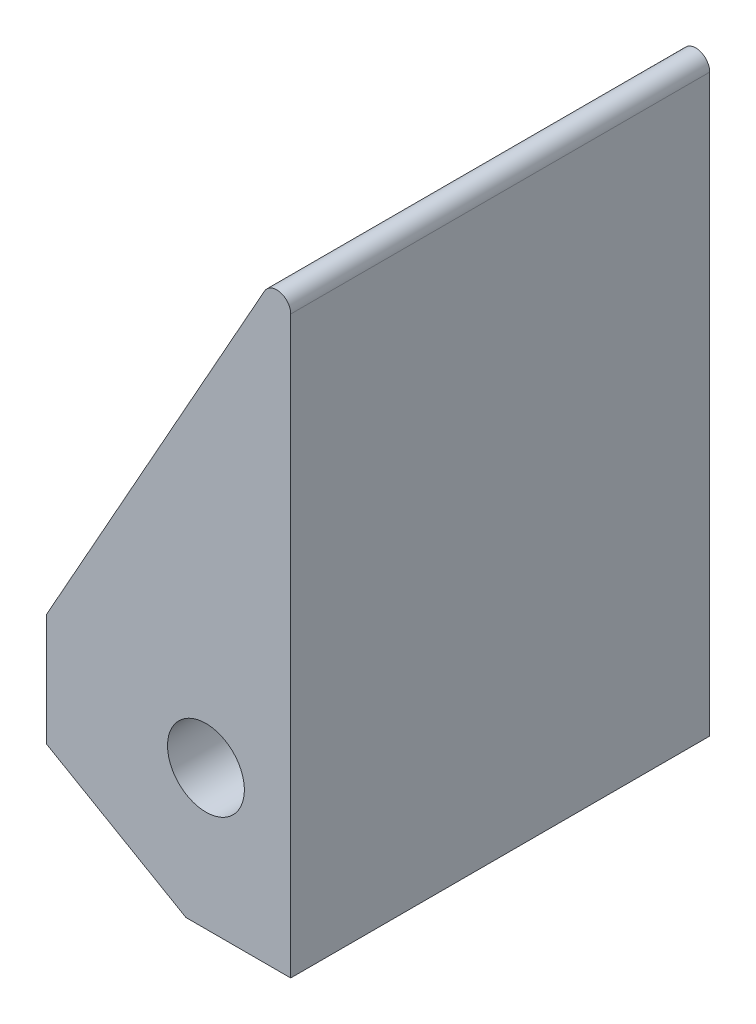
SolidWorks part; units mm, degrees
ref_plane "Front Plane" through (0, 0, 0) normal (0, 0, 1) x (1, 0, 0)
ref_plane "Top Plane" through (0, 0, 0) normal (0, 1, 0) x (1, 0, 0)
ref_plane "Right Plane" through (0, 0, 0) normal (1, 0, 0) x (0, 0, -1)
sketch "Sketch1" plane through (0, 0, 0) normal (0, 0, 1) x (1, 0, 0)
  line L0 (-8.1502, -18.2688) -> (1.8498, -24.0423)
  line L1 (1.8498, -24.0423) -> (9.3498, -24.0423)
  line L2 (-8.1502, -18.2688) -> (-8.1502, -10.2688)
  line L4 (9.3498, -24.0423) -> (9.3498, 20.9577)
  line L5 (-8.1502, -18.2688) -> (9.3498, 20.9577) construction
  line L6 (-0.9813, 2.5233) -> (9.3498, -24.0423) construction
  line L7 (-8.1502, -10.2688) -> (9.3498, 20.9577)
  point P0 (0, 0)
  dimension "D1" = 17.5
  dimension "D2" = 45
  dimension "D3" = 30
  dimension "D4" = 7.5
  dimension "D5" = 8
extrude "Boss-Extrude1" add sketch "Sketch1" along normal blind 30
sketch "Sketch2" plane through (0, 0, 0) normal (0, 0, -1) x (-1, 0, 0)
  line L0 (-1.8498, -24.0423) -> (-9.3498, -24.0423) construction
  line L1 (8.1502, -10.2688) -> (8.1502, -18.2688) construction
  circle A0 centre (-3.2798, -14.0423) radius 2.75
  circle A1 centre (-3.2798, -20.3923) radius 2
  dimension "D1" = 5.5
  dimension "D2" = 4
  dimension "D3" = 6.35
  dimension "D4" = 10
  dimension "D6" = 11.43
extrude "Cut-Extrude1" cut sketch "Sketch2" against normal through all contours A0 region at (3.2798, -14.0423, 0)
extrude "Cut-Extrude2" cut sketch "Sketch2<3>" against normal blind 11 contours A1 region at (3.2798, -20.3923, 0)
sketch "Sketch2<3>" plane through (0, 0, 0) normal (0, 0, -1) x (-1, 0, 0) same geometry as "Sketch2"
hole_wizard "M2.5x0.45 Tapped Hole1" positions "Sketch3" profile "Sketch5" tap size "M2.5x0.45" standard "ANSI Metric"
sketch "Sketch3" plane through (0, -24.0423, 0) normal (0, -1, 0) x (-1, 0, 0)
  line L2 (-1.8498, 0) -> (-9.3498, 0) construction
  point P0 (-5.5998, -16)
  point P14 (-5.5998, 0)
  dimension "D1" = 0
  dimension "D2" = 16
sketch "Sketch5" plane through (5.5998, -24.0423, 16) normal (1, 0, 0) x (0, 0, -1)
  line L0 (0, 0) -> (0, 8.1159)
  line L1 (0, 8.1159) -> (1.025, 7.5)
  line L2 (1.025, 7.5) -> (1.025, 0.25)
  line L3 (1.025, 0.25) -> (1.275, 0)
  line L5 (1.275, 0) -> (0, 0)
  line L6 (-1.025, 0.25) -> (-1.275, 0) construction
  line L10 (0, 8.1159) -> (-1.025, 7.5) construction
  line L11 (0, -6.35) -> (0, 107.95) construction
  dimension "Tap Drill Dia." = 2.05
  dimension "Tap Drill Depth" = 7.5
  dimension "Near C'Sink Dia." = 2.55
  dimension "Near C'Sink Angle" = 90
  dimension "Drill Angle" = 118
cosmetic thread "Hole Thread1" parameters "D1"=5, "D2"=2.5
fillet "Fillet1" radius 1 1 edges at (9.3498, 20.9577, 15)
